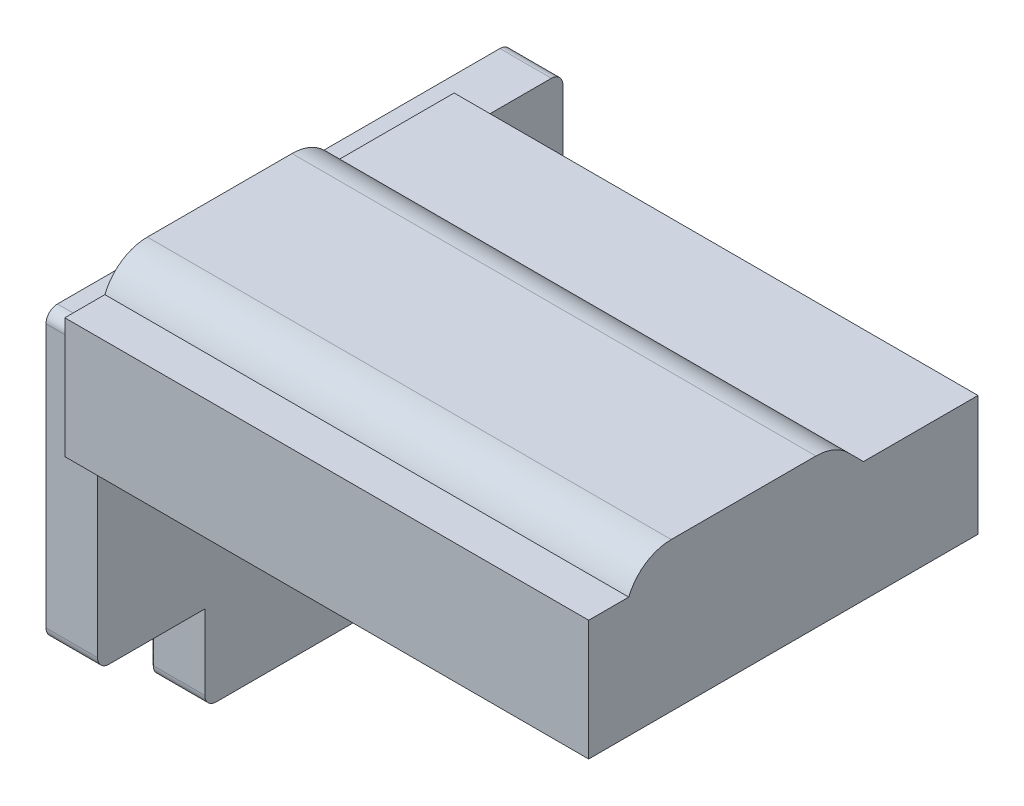
SolidWorks part; units mm, degrees
ref_plane "Front Plane" through (0, 0, 0) normal (0, 0, 1) x (1, 0, 0)
ref_plane "Top Plane" through (0, 0, 0) normal (0, 1, 0) x (1, 0, 0)
ref_plane "Right Plane" through (0, 0, 0) normal (1, 0, 0) x (0, 0, -1)
sketch "Sketch1" plane through (0, 0, 0) normal (0, 1, 0) x (1, 0, 0)
  line L1 (-457.5, 680) -> (457.5, 680)
  line L2 (-457.5, 680) -> (-457.5, 0)
  line L3 (-457.5, 0) -> (457.5, 0)
  line L4 (457.5, 680) -> (457.5, 0)
  point P4 (0, 680)
  dimension "D1" = 680
  dimension "D2" = 915
extrude "Boss-Extrude1" add sketch "Sketch1" against normal blind 210
sketch "Sketch3" plane through (-457.5, 0, 0) normal (-1, 0, 0) x (0, 0, 1)
  line L1 (-680, 0) -> (0, 0) construction
  line L2 (-70, 0) -> (-430, 0)
  line L3 (-70, 0) -> (-70, 50)
  line L4 (-70, 50) -> (-430, 50)
  line L5 (-430, 0) -> (-430, 50)
  line L6 (0, -210) -> (0, 0) construction
  line L7 (-430, 50) -> (-480, 0)
  line M1 (0, 0) -> (-680, 0)
  dimension "D2" = 70
  dimension "D1" = 50
  dimension "D3" = 360
  dimension "D4" = 50
extrude "Boss-Extrude2" add sketch "Sketch3" against normal up to surface (915 mm away) contours L5 L3 L4 M1 | L5 L7 M1 up to face at (457.5, -105, -340)
fillet "Fillet1" radius 80 2 edges at (0, 50, -70) (0, 50, -430)
sketch "Sketch4" plane through (0, 50, 0) normal (0, 1, 0) x (1, 0, 0)
  line L0 (-457.5, 270.5124) -> (457.5, 270.5124)
  line L1 (-457.5, 144.162) -> (-457.5, 396.8629) construction
  line L2 (457.5, 144.162) -> (457.5, 396.8629) construction
sketch3d "3DSketch1"
  line L0 (0, 50, -270.5124) -> (0, -210, -270.5124)
  line L1 (-457.5, 50, -270.5124) -> (457.5, 50, -270.5124) construction
  line L2 (457.5, 50, -270.5124) -> (-457.5, 50, -270.5124)
  line L3 (457.5, 50, -144.162) -> (457.5, 50, -396.8629) construction
  line L4 (-457.5, 50, -144.162) -> (-457.5, 50, -396.8629) construction
  line L5 (0, 50, -144.162) -> (0, 50, -396.8629)
  line L6 (-457.5, 50, -144.162) -> (457.5, 50, -144.162) construction
  line L7 (457.5, 50, -396.8629) -> (-457.5, 50, -396.8629) construction
sketch "Sketch5" plane through (-457.5, 0, 0) normal (-1, 0, 0) x (0, 0, 1)
  line L0 (0, -210) -> (0, 0) construction
  line L1 (-57.15, -62.68) -> (-869.95, -62.68)
  line L2 (-57.15, -62.68) -> (-57.15, -562.68)
  line L3 (-57.15, -562.68) -> (-869.95, -562.68)
  line L4 (-869.95, -62.68) -> (-869.95, -562.68)
  line L5 (-682.625, -562.68) -> (-244.475, -562.68)
  line L6 (-682.625, -562.68) -> (-682.625, -713.405)
  line L7 (-682.625, -713.405) -> (-244.475, -713.405)
  line L8 (-244.475, -562.68) -> (-244.475, -713.405)
  line L9 (-680, -210) -> (0, -210) construction
  line L10 (-682.625, -713.405) -> (-869.95, -713.405)
  line L11 (-869.95, -713.405) -> (-869.95, -562.68)
  line L12 (-244.475, -713.405) -> (-57.15, -713.405)
  line L13 (-57.15, -713.405) -> (-57.15, -562.68)
  line M13 (-680, 0) -> (-680, -210)
  line M14 (-680, -210) -> (0, -210)
  dimension "D1" = 57.15
  dimension "D2" = 147.32
  dimension "D3" = 650.725
  dimension "D4" = 500
  dimension "D6" = 812.8
  dimension "D7" = 438.15
extrude "Boss-Extrude3" add sketch "Sketch5" along normal blind 90 separate body contours L1 L4 L3 L2 M14 M13 | L8 L3 L6 L7 | L2 L1 M13 M14 region at (-457.5, -136.34, -368.575) region at (-457.5, -364.1056, -491.2473) region at (-457.5, -638.0425, -463.55)
fillet "Fillet2" radius 20 6 edges at (-502.5, -62.68, -57.15) (-502.5, -562.68, -57.15) (-502.5, -713.405, -244.475) (-502.5, -713.405, -682.625) (-502.5, -562.68, -869.95) (-502.5, -62.68, -869.95)
